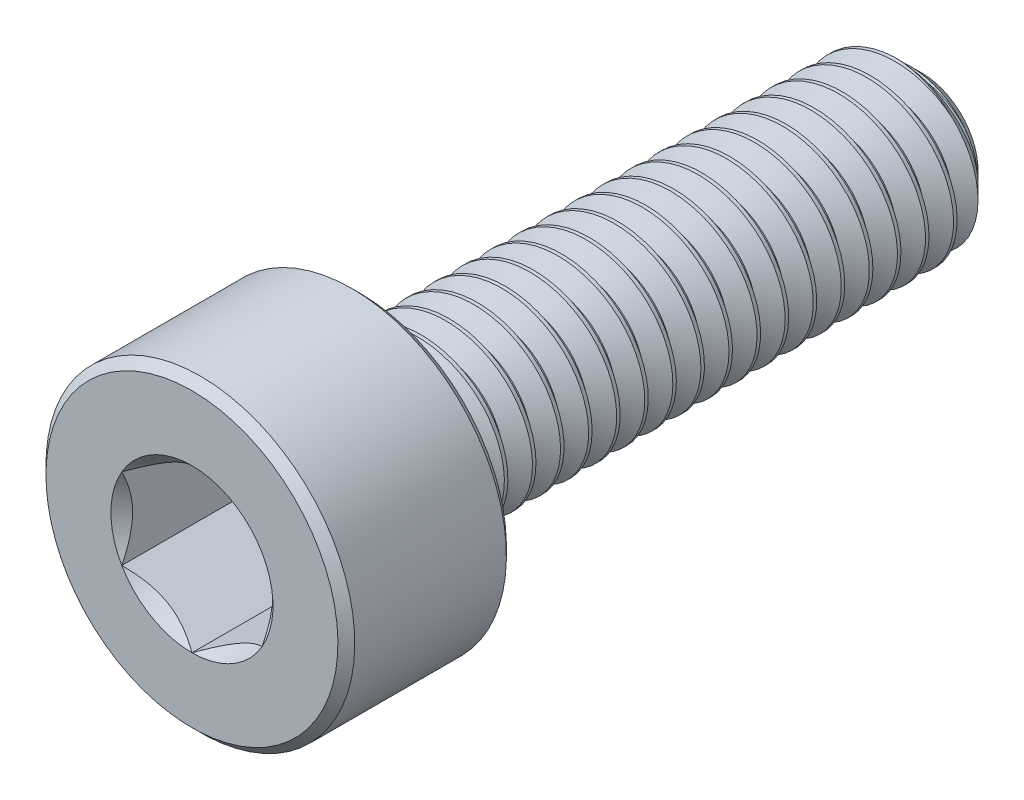
SolidWorks part; units mm, degrees
ref_plane "Front Plane" through (0, 0, 0) normal (0, 0, 1) x (1, 0, 0)
ref_plane "Top Plane" through (0, 0, 0) normal (0, 1, 0) x (1, 0, 0)
ref_plane "Right Plane" through (0, 0, 0) normal (1, 0, 0) x (0, 0, -1)
sketch "Sketch1" plane through (0, 0, 0) normal (1, 0, 0) x (0, 0, -1)
  line L0 (-6.5, 0) -> (6.5, 0) construction
  line L1 (6.5, 0) -> (6.5, 1) construction
  line L2 (6.5, 1) -> (6, 1.5) construction
  line L3 (6, 1.5) -> (6.125, 1.5) construction
  line L4 (6.125, 1.5) -> (-3.5, 1.5) construction
  line L5 (-3.5, 1.5) -> (-3.5, 2.75) construction
  line L6 (-3.5, 2.75) -> (-6.5, 2.75) construction
  line L7 (-6.5, 2.75) -> (-6.5, 0) construction
  line L8 (6.5, 1) -> (6.5, 1.5) construction
  line L9 (6.4688, 1.5541) -> (6.7188, 1.1211) construction
  line L10 (6.7188, 1.1211) -> (6.9688, 1.5541) construction
  line L11 (6.9688, 1.5541) -> (6.4688, 1.5541) construction
  line L12 (6.7187, 1.5541) -> (6.7188, 1.5) construction
  line L13 (6.7188, 1.1211) -> (6.7188, 1.1752) construction
  line L14 (6.6875, 1.1752) -> (6.75, 1.1752) construction
  line L15 (6.5, 1.5) -> (6.9375, 1.5) construction
  line L16 (6.4844, 1.5271) -> (6.9531, 1.5271) construction
  line L17 (6.5, 0) -> (6.5, -1.5) construction
  line L18 (-3.65, 2.75) -> (-3.5, 2.6) construction
  line L19 (-6.35, 2.75) -> (-6.5, 2.6) construction
  line L20 (-3.5, 1.5) -> (-3.5, 0) construction
  line L21 (-3.5, 0.75) -> (-0.1667, 0.75) construction
  line L22 (-0.1667, 0.75) -> (3.1667, 0.75) construction
  line L23 (3.1667, 0.75) -> (6.5, 0.75) construction
  line L24 (-0.1667, 0.75) -> (-0.1667, 1.5) construction
  line L25 (-0.1667, 1.5) -> (-0.1667, 2.75) construction
  line L26 (3.1667, 0.75) -> (3.1667, 2.75) construction
  point P0 (-6.5, 1.25)
  point P3 (5.25, 1.5)
  point P4 (0, 0)
  point P18 (3.1667, 1.5)
  point P22 (6.7188, 1.1752)
  point P24 (6.125, 1.5)
  point P25 (6.7188, 1.5)
  point P28 (6.7188, 1.5271)
  point P29 (5.25, -1.5)
  point P30 (-0.1667, 1.5)
  point P31 (-5, 2.75)
  point P37 (-4.025, 2.75)
  point P38 (-6.275, 2.75)
  point P45 (-0.1667, 0.75)
  point P46 (3.1667, 0.75)
  dimension "D1" = 45
  dimension "D2" = 0.0625
  dimension "D3" = 0.5
  dimension "D7" = 0.15
  dimension "D8" = 0.15
  dimension "D9" = 0.15
  dimension "D10" = 0.075
  dimension "D11" = 0.375
  dimension "Drive Size" = 2.5
  dimension "Head Diameter" = 5.5
  dimension "Head Height" = 3
  dimension "Thread Pitch" = 0.5
  dimension "Thread Major Diameter" = 3
  dimension "Length" = 10
  dimension "D12" = 0.375
  dimension "D4" = 1.25
sketch "Sketch2" plane through (0, 0, 0) normal (1, 0, 0) x (0, 0, -1)
  line L0 (-6.5, 0) -> (-6.5, 2.6)
  line L1 (-6.35, 2.75) -> (-3.65, 2.75)
  line L2 (-3.5, 2.6) -> (-3.5, 1.5)
  line L3 (-3.5, 1.5) -> (6, 1.5)
  line L4 (6, 1.5) -> (6.5, 1)
  line L5 (6.5, 1) -> (6.5, 0)
  line L6 (-3.65, 2.75) -> (-3.5, 2.6) construction
  line L7 (6.5, 0) -> (-6.5, 0)
  line L8 (-6.35, 2.75) -> (-6.5, 2.6) construction
  line L9 (-3.65, 2.75) -> (-3.5, 2.6)
  line L10 (-6.35, 2.75) -> (-6.5, 2.6)
revolve "Revolve1" add sketch "Sketch2" angle 360 about L7
sketch "Sketch3" plane through (0, 0, 6.5) normal (0, 0, 1) x (1, 0, 0)
  line L1 (1.25, -0.7217) -> (1.25, 0.7217)
  line L2 (1.25, 0.7217) -> (0, 1.4434)
  line L3 (0, 1.4434) -> (-1.25, 0.7217)
  line L4 (-1.25, 0.7217) -> (-1.25, -0.7217)
  line L5 (-1.25, -0.7217) -> (0, -1.4434)
  line L6 (0, -1.4434) -> (1.25, -0.7217)
  circle A0 centre (0, 0) radius 1.25 construction
extrude "Cut-Extrude1" cut sketch "Sketch3" against normal offset from surface (2 mm away) 1 up to face at (0, 2.6, 3.5)
sketch "Sketch4" plane through (0, 0, 6.5) normal (0, 0, 1) x (1, 0, 0)
  circle A0 centre (0, 0) radius 1.4434
extrude "Cut-Extrude2" cut sketch "Sketch4" against normal up to vertex (1.5 mm away) draft 45 up to point (0, 2.75, 5)
ref_plane "Plane1" through (0, 0, -6.125) normal (0, 0, 1) x (1, 0, 0)
split "Split1" bodies to split 106 resulting bodies 107 108 split by face at (0, 2.6, 3.5)
sketch "Sketch6" plane through (0, 0, -6.5) normal (0, 0, -1) x (-1, 0, 0)
  circle A0 centre (0, 0) radius 1.5
curve "Helix/Spiral1" pitch 0.5 height 15.575 radius 1.5 centre (0, 0, -6.5) axis (0, 0, 1) start towards (0, 1, 0)
sketch "Sketch7" plane through (0, 0, 0) normal (1, 0, 0) x (0, 0, -1)
  line L0 (6.4844, 1.5271) -> (6.9531, 1.5271)
  line L1 (6.9531, 1.5271) -> (6.75, 1.1752)
  line L2 (6.75, 1.1752) -> (6.6875, 1.1752)
  line L3 (6.6875, 1.1752) -> (6.4844, 1.5271)
sweep "Cut-Sweep1" cut profiles "Sketch7" path "Helix/Spiral1" align with end faces yes
sketch "Sketch8" plane through (0, 0, 3.5) normal (0, 0, -1) x (-1, 0, 0)
  circle A0 centre (0, 0) radius 1.5
extrude "Boss-Extrude1" add sketch "Sketch8" along normal through all draft 45
equation "\"D2@Sketch1\" = \"Thread Pitch@Sketch1\" / 8"
equation "\"D3@Sketch1\"= \"Thread Pitch@Sketch1\""
equation "\"D4@Helix/Spiral1\" = \"Thread Pitch@Sketch1\""
equation "\"D7@Sketch1\" = \"Head Height@Sketch1\" * .05"
equation "\"D8@Sketch1\"=\"D7@Sketch1\""
equation "\"D9@Sketch1\"=\"D7@Sketch1\""
equation "\"D10@Sketch1\"=\"D7@Sketch1\"/2"
equation "\"D11@Sketch1\"=\"D10@Sketch1\"*5"
equation "\"D4@Sketch1\"=\"Thread Pitch@Sketch1\"*2.5"
equation "\"D12@Sketch1\"=\"Thread Pitch@Sketch1\"*.75"
